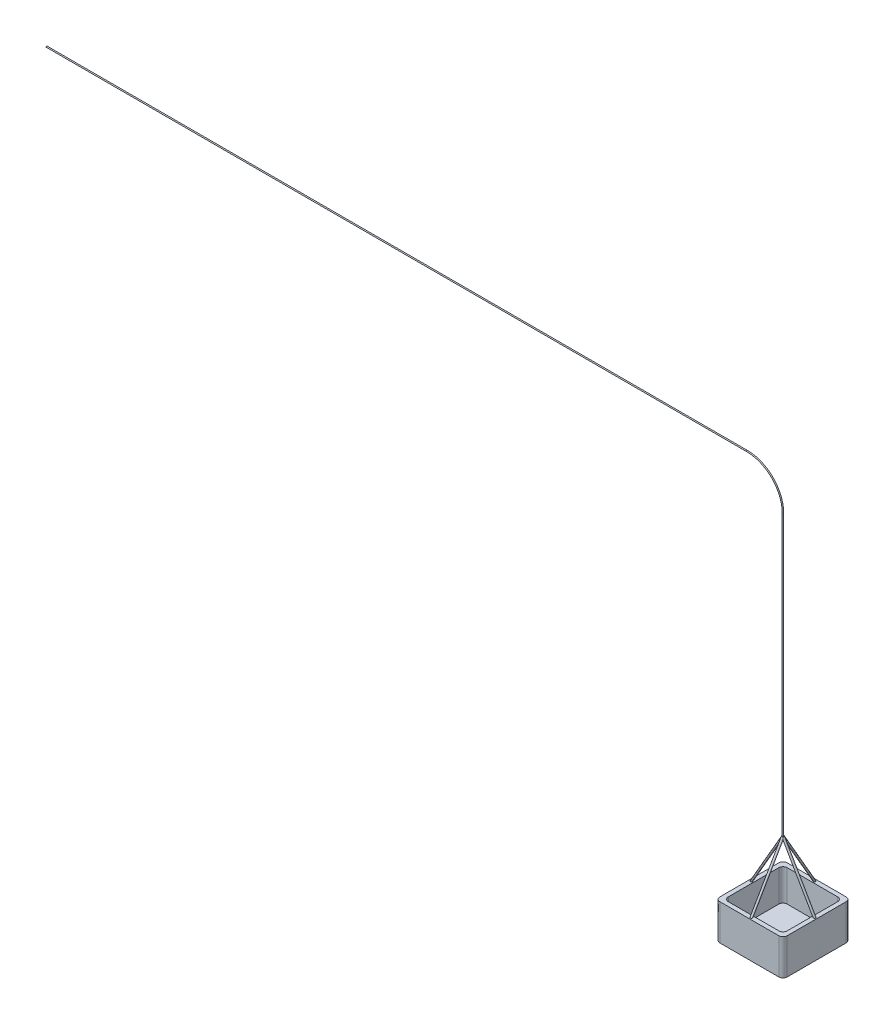
SolidWorks part; units mm, degrees
material "ABS"
ref_plane "Front Plane" through (0, 0, 0) normal (0, 0, 1) x (1, 0, 0)
ref_plane "Top Plane" through (0, 0, 0) normal (0, 1, 0) x (1, 0, 0)
ref_plane "Right Plane" through (0, 0, 0) normal (1, 0, 0) x (0, 0, -1)
sketch "Sketch1" plane through (0, 0, 0) normal (0, 0, 1) x (1, 0, 0)
  line L0 (0, 0) -> (332.92, 0)
  line L1 (350, -17.08) -> (350, -150)
  arc A0 (332.92, 0) -> (350, -17.08) centre (332.92, -17.08) cw
  point P1 (0, 0)
  point P3 (0, 0)
  point P6 (350, 0)
  dimension "D3" = 17.08
  dimension "D1" = 350
  dimension "D2" = 150
sketch "Sketch2" plane through (0, 0, 0) normal (1, 0, 0) x (0, 0, -1)
  circle A0 centre (0, 0) radius 0.25
  dimension "D1" = 0.5
sweep "Sweep1" add profiles "Sketch2" path "Sketch1"
ref_axis "Axis1" through (350, -17.08, 0) along (0, -1, 0)
ref_plane "Plane1" through (0, 0, 0) normal (0, 0, 1) x (0, -1, 0)
sketch "Sketch3" plane through (0, 0, 0) normal (0, 0, 1) x (0, -1, 0)
  line L0 (150, 350) -> (175.9808, 365)
  line L1 (150, 349.75) -> (150, 350.25) construction
  line L2 (150, 350) -> (74.7177, 350) construction
  line L3 (17.08, 350) -> (150, 350) construction
  point P7 (0, 0)
  dimension "D1" = 30
  dimension "D2" = 30
ref_plane "Plane2" through (0, -175.9808, 0) normal (0, 1, 0) x (1, 0, 0)
sketch "Sketch4" plane through (0, -175.9808, 0) normal (0, 1, 0) x (1, 0, 0)
  circle A0 centre (365, 0) radius 0.5
  dimension "D1" = 1
sweep "Sweep2" add profiles "Sketch4" path "Sketch3"
pattern_circular "CirPattern1" count 4 over 360 about axis through (350, -17.08, 0) along (0, -1, 0) of "Sweep2"
sketch "Sketch5" plane through (0, -175.9808, 0) normal (0, -1, 0) x (1, 0, 0)
  line L1 (334, 16) -> (366, 16)
  line L2 (334, 16) -> (334, -16)
  line L3 (334, -16) -> (366, -16)
  line L4 (366, 16) -> (366, -16)
  line L5 (336, 14) -> (364, 14)
  line L6 (336, 14) -> (336, -14)
  line L7 (336, -14) -> (364, -14)
  line L8 (364, 14) -> (364, -14)
  point P4 (135.044, 16.292)
  point P9 (137.3562, 16.4336)
  point P10 (136.0821, 16.3392)
  point P12 (136.6484, 16.528)
  point P13 (140.8481, 14.9707)
  dimension "D1" = 32
  dimension "D2" = 32
  dimension "D3" = 2
  dimension "D4" = 2
  dimension "D5" = 2
  dimension "D6" = 2
  dimension "D7" = 16
  dimension "D8" = 16
extrude "Boss-Extrude1" add sketch "Sketch5" along normal blind 15
sketch "Sketch6" plane through (0, -190.9808, 0) normal (0, -1, 0) x (1, 0, 0)
  line L4 (334, 16) -> (334, -16)
  line L5 (334, -16) -> (366, -16)
  line L6 (366, -16) -> (366, 16)
  line L7 (366, 16) -> (334, 16)
  line L8 (334, 16) -> (334, -16)
  line L9 (334, -16) -> (366, -16)
  line L10 (366, -16) -> (366, 16)
  line L11 (366, 16) -> (334, 16)
  dimension "D1" = 0
extrude "Boss-Extrude2" add sketch "Sketch6" along normal blind 2
fillet "Fillet1" radius 2 8 edges at (366, -184.4808, 16) (336, -183.4808, 14) (336, -183.4808, -14) (364, -183.4808, -14) (334, -184.4808, 16) (366, -184.4808, -16) (364, -183.4808, 14) (334, -184.4808, -16)
sketch "Sketch7" plane through (0, 0, 0) normal (0, 0, 1) x (1, 0, 0)
  circle A0 centre (332.92, -17.08) radius 17.08
